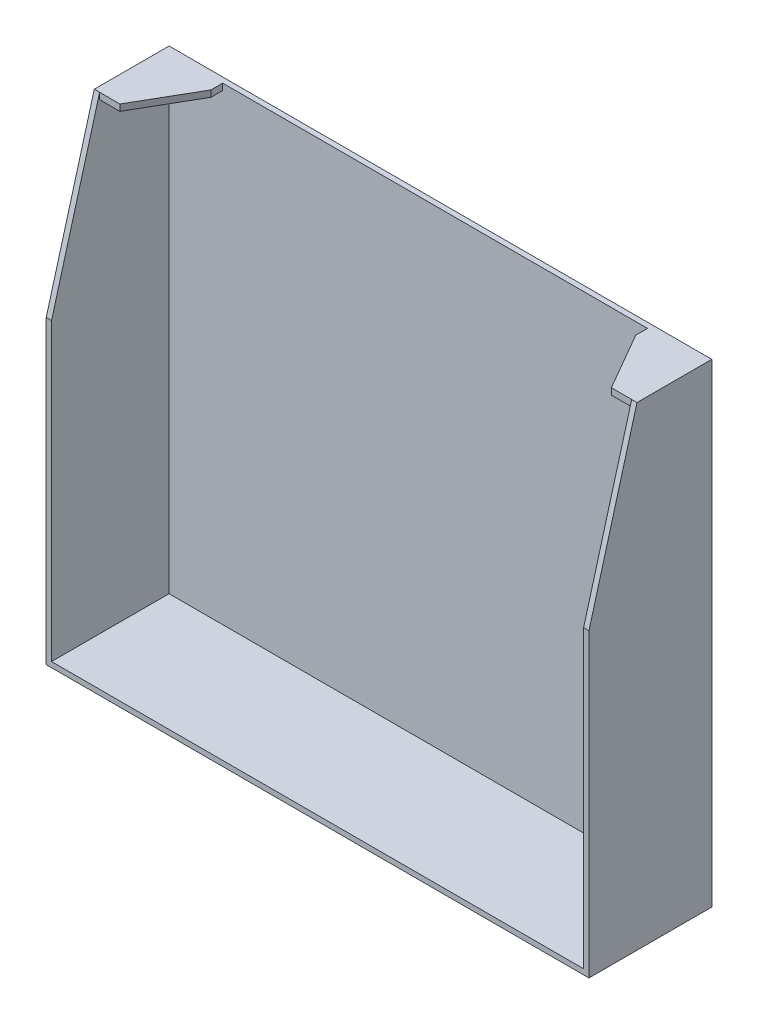
SolidWorks part; units mm, degrees
ref_plane "Front" through (0, 0, 0) normal (0, 0, 1) x (1, 0, 0)
ref_plane "Top" through (0, 0, 0) normal (0, 1, 0) x (1, 0, 0)
ref_plane "Right" through (0, 0, 0) normal (1, 0, 0) x (0, 0, -1)
sketch "Sketch1" plane through (0, 0, 0) normal (0, 0, 1) x (1, 0, 0)
  line L1 (-127, -111) -> (127, -111)
  line L2 (-127, -111) -> (-127, 111)
  line L3 (-127, 111) -> (127, 111)
  line L4 (127, -111) -> (127, 111)
  line L5 (-127, -111) -> (127, 111) construction
  line L6 (-127, 111) -> (127, -111) construction
  point P0 (0, 0)
  dimension "D1" = 222
  dimension "D2" = 254
extrude "Boss-Extrude1" add sketch "Sketch1" against normal blind 2.5
sketch "Sketch2" plane through (0, 0, 0) normal (0, 0, 1) x (1, 0, 0)
  line L0 (-127, -111) -> (127, -111) construction
  line L1 (-127, 111) -> (-124.5, 111)
  line L2 (-127, 111) -> (-127, -111)
  line L3 (-127, -111) -> (-124.5, -111)
  line L4 (-124.5, 111) -> (-124.5, -111)
  line L6 (127, 111) -> (124.5, 111)
  line L7 (127, 111) -> (127, -111)
  line L8 (127, -111) -> (124.5, -111)
  line L9 (124.5, 111) -> (124.5, -111)
  line L10 (-124.5, 111) -> (124.5, 111)
  line L14 (-124.5, -111) -> (124.5, -111)
  line L15 (-124.5, -111) -> (-124.5, -108.5)
  line L16 (-124.5, -108.5) -> (124.5, -108.5)
  line L17 (124.5, -111) -> (124.5, -108.5)
  dimension "D1" = 2.5
extrude "Boss-Extrude2" add sketch "Sketch2" along normal blind 55 contours L4 L1 L2 L3 | L16 L4 L14 L9 | L6 L9 L8 L7 region at (-125.75, 0, 0) region at (0, -109.75, 0) region at (125.75, 0, 0)
sketch "Sketch4" plane through (0, 111, 0) normal (0, 1, 0) x (1, 0, 0)
  line L0 (127, 2.5) -> (127, -32.5)
  line L1 (127, 2.5) -> (127, -55) construction
  line L2 (127, -32.5) -> (115, -32.5)
  line L3 (115, -32.5) -> (99.4115, -5.5)
  line L4 (99.4115, -5.5) -> (99.4115, 2.5)
  line L5 (127, 2.5) -> (-127, 2.5) construction
  line L6 (99.4115, 2.5) -> (127, 2.5)
  point P5 (127, -31.9323)
  dimension "D1" = 60
  dimension "D2" = 35
  dimension "D3" = 12
  dimension "D4" = 8
extrude "Hold Tab" add sketch "Sketch4" against normal blind 3
mirror "Hold Tabs" about plane through (0, 0, 0) normal (1, 0, 0) of "Hold Tab"
sketch "Sketch5" plane through (0, 0, 0) normal (1, 0, 0) x (0, 0, -1)
  line L0 (-55, 29.728) -> (-32.5, 111)
  line L1 (-55, 111) -> (-55, -111) construction
  line L2 (2.5, 111) -> (-55, 111) construction
  line L3 (-32.5, 111) -> (-55, 111)
  line L4 (-55, 111) -> (-55, 29.728)
extrude "Front Taper" cut sketch "Sketch5" against normal through all both and the other way through all
